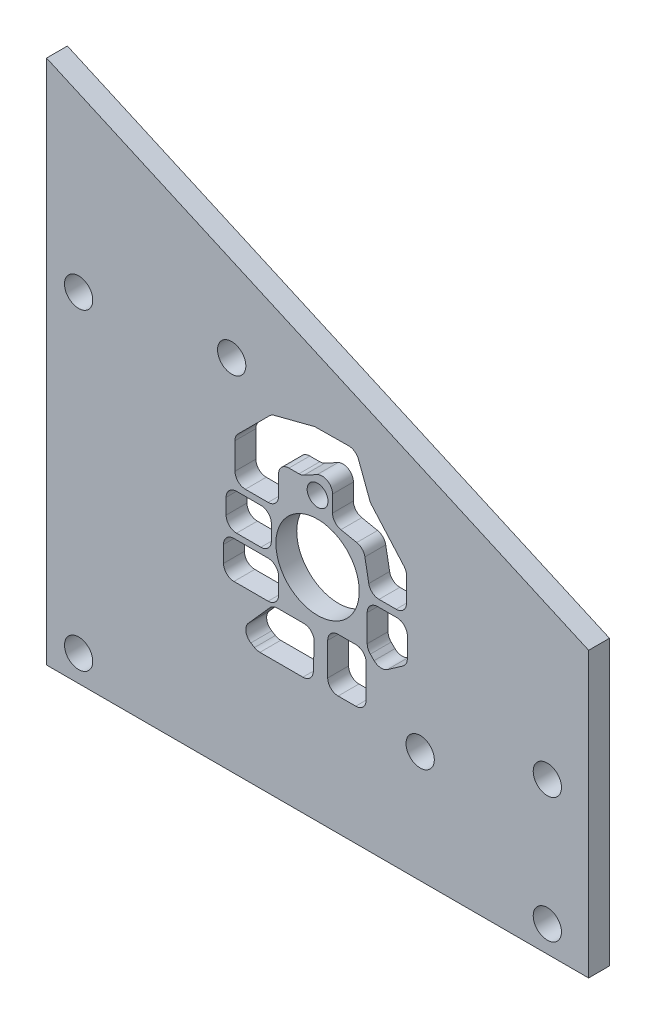
SolidWorks part; units mm, degrees
ref_plane "Front Plane" through (0, 0, 0) normal (0, 0, 1) x (1, 0, 0)
ref_plane "Top Plane" through (0, 0, 0) normal (0, 1, 0) x (1, 0, 0)
ref_plane "Right Plane" through (0, 0, 0) normal (1, 0, 0) x (0, 0, -1)
sketch "Sketch1" plane through (0, 0, 0) normal (0, 0, 1) x (1, 0, 0)
  line L16 (49.022, 13.462) -> (57.658, 13.462)
  line L17 (62.738, 8.382) -> (62.738, 0)
  line L18 (62.738, 0) -> (82.55, 0)
  line L19 (82.55, 0) -> (82.55, 58.42)
  line L20 (82.55, 58.42) -> (0, 95.25)
  line L21 (0, 95.25) -> (0, 0)
  line L22 (0, 0) -> (43.942, 0)
  line L23 (43.942, 0) -> (43.942, 8.382)
  arc A4 (62.738, 8.382) -> (57.658, 13.462) centre (57.658, 8.382) ccw
  arc A5 (49.022, 13.462) -> (43.942, 8.382) centre (49.022, 8.382) ccw
extrude "Boss-Extrude1" add sketch "Sketch1" against normal blind 3.175
hole_wizard "#6 Clearance Hole1" positions "Sketch3" profile "Sketch2" hole size "#6" standard "ANSI Inch" end condition through all
sketch "Sketch3" plane through (0, 0, -3.175) normal (0, 0, -1) x (-1, 0, 0)
  point P0 (-4.8895, 17.4625)
  point P4 (-4.8895, 65.0875)
  point P7 (-76.2635, 36.5125)
  point P10 (-76.2635, 17.4625)
  point P14 (-28.194, 68.072)
  point P17 (-56.896, 30.48)
sketch "Sketch2" plane through (4.8895, 17.4625, -3.175) normal (1, 0, 0) x (0, 1, 0)
  line L0 (0, 0) -> (0, 3.175)
  line L1 (0, 3.175) -> (2.1526, 3.175)
  line L2 (2.1526, 3.175) -> (2.1526, 0)
  line L5 (2.1526, 0) -> (0, 0)
  line L11 (0, -6.35) -> (0, 107.95) construction
  dimension "Thru Hole Dia." = 4.3053
  dimension "Thru Hole Depth" = 3.175
hole_wizard "1/2 (0.5) Diameter Hole1" positions "Sketch5" profile "Sketch4" hole size "1/2" standard "ANSI Inch" end condition through all
sketch "Sketch5" plane through (0, 0, -3.175) normal (0, 0, -1) x (-1, 0, 0)
  point P0 (-41.275, 46.99)
sketch "Sketch4" plane through (41.275, 46.99, -3.175) normal (1, 0, 0) x (0, 1, 0)
  line L0 (0, 0) -> (0, 3.175)
  line L1 (0, 3.175) -> (6.35, 3.175)
  line L2 (6.35, 3.175) -> (6.35, 0)
  line L5 (6.35, 0) -> (0, 0)
  line L11 (0, -6.35) -> (0, 107.95) construction
  dimension "Thru Hole Dia." = 12.7
  dimension "Thru Hole Depth" = 3.175
hole_wizard "1/8 (0.125) Diameter Hole1" positions "Sketch7" profile "Sketch6" hole size "1/8" standard "ANSI Inch" end condition through all
sketch "Sketch7" plane through (0, 0, 0) normal (0, 0, 1) x (1, 0, 0)
  point P0 (41.275, 56.4889)
sketch "Sketch6" plane through (41.275, 56.4889, 0) normal (1, 0, 0) x (0, -1, 0)
  line L0 (0, 0) -> (0, 3.175)
  line L1 (0, 3.175) -> (1.5875, 3.175)
  line L2 (1.5875, 3.175) -> (1.5875, 0)
  line L5 (1.5875, 0) -> (0, 0)
  line L11 (0, -6.35) -> (0, 107.95) construction
  dimension "Thru Hole Dia." = 3.175
  dimension "Thru Hole Depth" = 3.175
sketch "Sketch9" plane through (0, 0, 0) normal (0, 0, 1) x (1, 0, 0)
  line L1 (82.55, 58.42) -> (0, 95.25) construction
  line L2 (81.9032, 56.9702) -> (-0.6468, 93.8002)
  line L3 (82.55, 56.6817) -> (0, 93.5117)
  line L4 (82.55, 58.42) -> (0, 95.25)
  line L5 (82.55, 0) -> (82.55, 58.42) construction
  line L6 (0, 95.25) -> (0, 0) construction
  line L7 (0, 95.25) -> (0, 93.5117)
  line L8 (82.55, 58.42) -> (82.55, 56.6817)
  dimension "D1" = 1.5875
extrude "Cut-Extrude1" cut sketch "Sketch9" against normal through all
sketch "Sketch10" plane through (0, 0, 0) normal (0, 0, 1) x (1, 0, 0)
  line L0 (0, 93.5117) -> (0, 0) construction
  line L1 (82.55, 0) -> (0, 0)
  line L2 (82.55, 0) -> (82.55, 13.462)
  line L3 (82.55, 13.462) -> (0, 13.462)
  line L4 (0, 0) -> (0, 13.462)
  line L5 (49.022, 13.462) -> (57.658, 13.462) construction
extrude "Cut-Extrude2" cut sketch "Sketch10" against normal through all
sketch "Sketch11" plane through (0, 0, -3.175) normal (0, 0, -1) x (-1, 0, 0)
  line L0 (-47.4994, 64.35) -> (-49.2178, 59.797)
  line L1 (-49.5116, 59.3085) -> (-54.4247, 53.7282)
  line L2 (-54.8207, 52.6791) -> (-54.8207, 49.0282)
  line L3 (-53.2332, 47.4407) -> (-50.632, 47.4407)
  line L4 (-49.0704, 48.7427) -> (-48.481, 51.9664)
  line L5 (-47.2367, 53.2364) -> (-44.8263, 53.7281)
  line L6 (-43.556, 55.2835) -> (-43.556, 57.7887)
  line L10 (-35.3315, 56.3146) -> (-35.3315, 53.3713)
  line L11 (-33.744, 51.7838) -> (-30.2845, 51.7838)
  line L12 (-28.697, 53.3713) -> (-28.697, 57.3946)
  line L13 (-29.1619, 58.5172) -> (-33.9603, 63.3155)
  line L14 (-34.685, 63.7298) -> (-40.6377, 65.2708)
  line L15 (-45.9965, 65.3769) -> (-41.0178, 65.3214)
  line L17 (-41.2134, 59.1851) -> (-39.1943, 58.0932)
  line L18 (-38.4391, 57.9021) -> (-36.919, 57.9021)
  line L19 (-32.6464, 50.8408) -> (-28.9301, 50.8408)
  line L20 (-34.2339, 49.2533) -> (-34.2339, 46.9055)
  line L21 (-32.6464, 45.318) -> (-28.9301, 45.318)
  line L22 (-27.3426, 46.9055) -> (-27.3426, 49.2533)
  line L23 (-35.3315, 42.8403) -> (-35.3315, 40.3434)
  line L24 (-33.744, 38.7559) -> (-28.5401, 38.7559)
  line L25 (-26.9526, 40.3434) -> (-26.9526, 42.8403)
  line L26 (-28.5401, 44.4278) -> (-33.744, 44.4278)
  line L27 (-39.176, 38.541) -> (-35.181, 38.541)
  line L28 (-33.9952, 38.009) -> (-30.7456, 34.3581)
  line L29 (-31.1146, 31.9414) -> (-31.6722, 31.6068)
  line L30 (-32.489, 31.3805) -> (-39.0389, 31.3805)
  line L31 (-40.6255, 32.9134) -> (-40.7626, 36.8989)
  line L32 (-42.8176, 33.1652) -> (-42.8176, 38.125)
  line L33 (-44.4051, 39.7125) -> (-47.0833, 39.7125)
  line L34 (-48.6708, 38.125) -> (-48.6708, 33.1652)
  line L35 (-47.0833, 31.5777) -> (-44.4051, 31.5777)
  line L36 (-49.8872, 38.9868) -> (-49.3079, 39.5556)
  line L37 (-48.8326, 40.6883) -> (-48.8326, 44.7971)
  line L38 (-50.4201, 46.3846) -> (-53.3578, 46.3846)
  line L39 (-54.9453, 44.7971) -> (-54.9453, 41.7679)
  line L40 (-54.2673, 40.4668) -> (-51.909, 38.8183)
  arc A0 (-28.697, 57.3946) -> (-29.1619, 58.5172) centre (-30.2845, 57.3946) ccw
  arc A1 (-30.2845, 51.7838) -> (-28.697, 53.3713) centre (-30.2845, 53.3713) ccw
  arc A2 (-35.3315, 53.3713) -> (-33.744, 51.7838) centre (-33.744, 53.3713) ccw
  arc A4 (-33.9603, 63.3155) -> (-34.685, 63.7298) centre (-35.0828, 62.193) ccw
  arc A5 (-47.4994, 64.35) -> (-45.9965, 65.3769) centre (-46.0142, 63.7895) cw
  arc A6 (-49.2178, 59.797) -> (-49.5116, 59.3085) centre (-50.7031, 60.3576) cw
  arc A7 (-54.4247, 53.7282) -> (-54.8207, 52.6791) centre (-53.2332, 52.6791) ccw
  arc A8 (-54.8207, 49.0282) -> (-53.2332, 47.4407) centre (-53.2332, 49.0282) ccw
  arc A9 (-50.632, 47.4407) -> (-49.0704, 48.7427) centre (-50.632, 49.0282) ccw
  arc A10 (-48.481, 51.9664) -> (-47.2367, 53.2364) centre (-46.9194, 51.6809) cw
  arc A11 (-44.8263, 53.7281) -> (-43.556, 55.2835) centre (-45.1435, 55.2835) ccw
  arc A13 (-40.6377, 65.2708) -> (-41.0178, 65.3214) centre (-41.0355, 63.734) ccw
  arc A14 (-36.919, 57.9021) -> (-35.3315, 56.3146) centre (-36.919, 56.3146) cw
  arc A15 (-39.1943, 58.0932) -> (-38.4391, 57.9021) centre (-38.4391, 59.4896) ccw
  arc A16 (-43.556, 57.7887) -> (-41.2134, 59.1851) centre (-41.9685, 57.7887) cw
  arc A17 (-28.9301, 50.8408) -> (-27.3426, 49.2533) centre (-28.9301, 49.2533) cw
  arc A18 (-28.9301, 45.318) -> (-27.3426, 46.9055) centre (-28.9301, 46.9055) ccw
  arc A19 (-34.2339, 46.9055) -> (-32.6464, 45.318) centre (-32.6464, 46.9055) ccw
  arc A20 (-32.6464, 50.8408) -> (-34.2339, 49.2533) centre (-32.6464, 49.2533) ccw
  arc A21 (-26.9526, 42.8403) -> (-28.5401, 44.4278) centre (-28.5401, 42.8403) ccw
  arc A22 (-28.5401, 38.7559) -> (-26.9526, 40.3434) centre (-28.5401, 40.3434) ccw
  arc A23 (-35.3315, 40.3434) -> (-33.744, 38.7559) centre (-33.744, 40.3434) ccw
  arc A24 (-35.3315, 42.8403) -> (-33.744, 44.4278) centre (-33.744, 42.8403) cw
  arc A25 (-39.0389, 31.3805) -> (-40.6255, 32.9134) centre (-39.0389, 32.968) cw
  arc A26 (-31.6722, 31.6068) -> (-32.489, 31.3805) centre (-32.489, 32.968) cw
  arc A27 (-30.7456, 34.3581) -> (-31.1146, 31.9414) centre (-31.9314, 33.3026) cw
  arc A28 (-35.181, 38.541) -> (-33.9952, 38.009) centre (-35.181, 36.9535) cw
  arc A29 (-39.176, 38.541) -> (-40.7626, 36.8989) centre (-39.176, 36.9535) ccw
  arc A30 (-48.6708, 33.1652) -> (-47.0833, 31.5777) centre (-47.0833, 33.1652) ccw
  arc A31 (-47.0833, 39.7125) -> (-48.6708, 38.125) centre (-47.0833, 38.125) ccw
  arc A32 (-42.8176, 38.125) -> (-44.4051, 39.7125) centre (-44.4051, 38.125) ccw
  arc A33 (-42.8176, 33.1652) -> (-44.4051, 31.5777) centre (-44.4051, 33.1652) cw
  arc A34 (-48.8326, 44.7971) -> (-50.4201, 46.3846) centre (-50.4201, 44.7971) ccw
  arc A35 (-49.3079, 39.5556) -> (-48.8326, 40.6883) centre (-50.4201, 40.6883) ccw
  arc A36 (-49.8872, 38.9868) -> (-51.909, 38.8183) centre (-50.9995, 40.1195) cw
  arc A37 (-54.9453, 41.7679) -> (-54.2673, 40.4668) centre (-53.3578, 41.7679) ccw
  arc A38 (-53.3578, 46.3846) -> (-54.9453, 44.7971) centre (-53.3578, 44.7971) ccw
  dimension "D1" = 1.5875
  dimension "D2" = 1.5875
  dimension "D3" = 1.5875
  dimension "D4" = 1.5875
  dimension "D5" = 1.5875
  dimension "D6" = 1.5875
  dimension "D7" = 1.5875
  dimension "D8" = 1.5875
extrude "Cut-Extrude3" cut sketch "Sketch11" against normal through all
